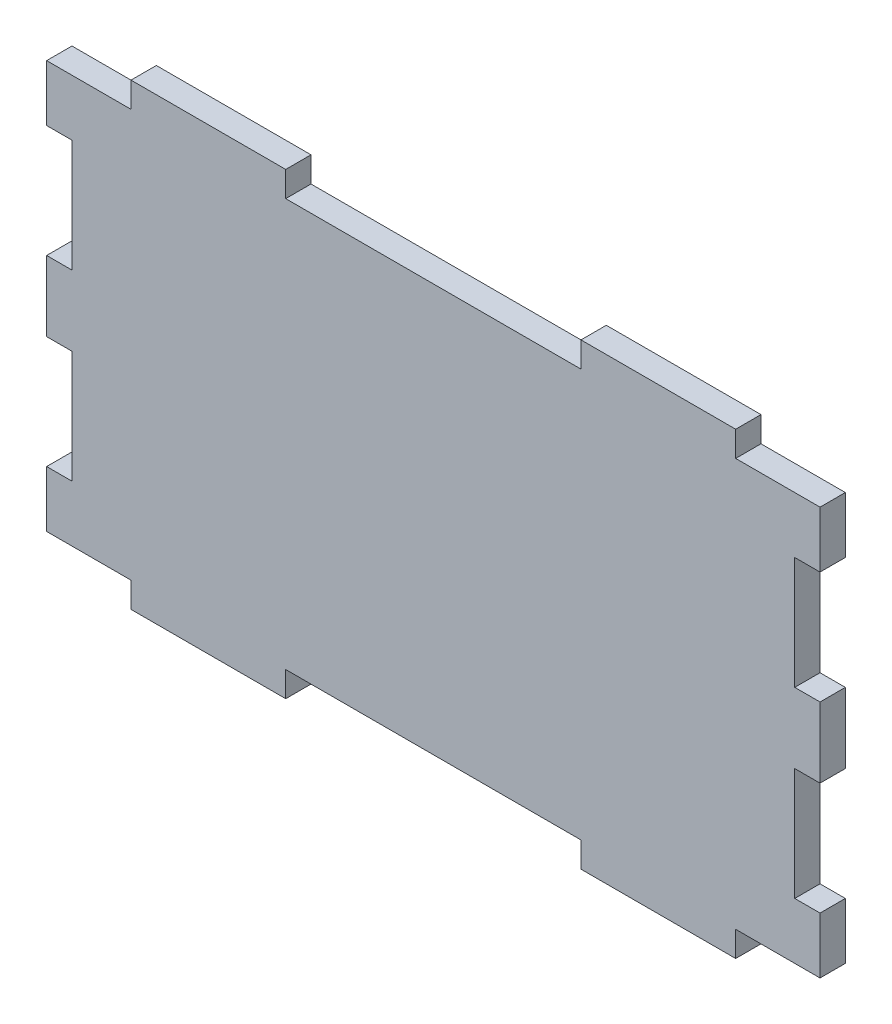
SolidWorks part; units mm, degrees
material "Бальса"
ref_plane "Спереди" through (0, 0, 0) normal (0, 0, 1) x (1, 0, 0)
ref_plane "Сверху" through (0, 0, 0) normal (0, 1, 0) x (1, 0, 0)
ref_plane "Справа" through (0, 0, 0) normal (1, 0, 0) x (0, 0, -1)
sketch "Эскиз1" plane through (0, 0, 0) normal (0, 0, 1) x (1, 0, 0)
  line L1 (0, 0) -> (110, 0)
  line L2 (0, 0) -> (0, 58)
  line L3 (0, 58) -> (110, 58)
  line L4 (110, 0) -> (110, 58)
  dimension "D1" = 110
  dimension "D2" = 58
base flange "Базовая кромка1" sketch "Эскиз1" thickness 3.6 reverse thickness direction no parameters "D1"=0.7366
sketch "Эскиз2" plane through (0, 0, -3.6) normal (0, 0, -1) x (-1, 0, 0)
  line L0 (-110, 0) -> (-110, 58) construction
  line L1 (-110, 50) -> (-106.4, 50)
  line L2 (-110, 50) -> (-110, 34)
  line L3 (-110, 34) -> (-106.4, 34)
  line L4 (-106.4, 50) -> (-106.4, 34)
  line L5 (-110, 0) -> (-110, 58) construction
  line L6 (-110, 24) -> (-106.4, 24)
  line L7 (-110, 24) -> (-110, 8)
  line L8 (-110, 8) -> (-106.4, 8)
  line L9 (-106.4, 24) -> (-106.4, 8)
  line L10 (-110, 58) -> (0, 58) construction
  line L11 (0, 0) -> (-110, 0) construction
  line L12 (-55, 58) -> (-55, 0) construction
  line L13 (-3.6, 24) -> (-3.6, 8)
  line L14 (0, 8) -> (-3.6, 8)
  line L15 (0, 24) -> (0, 8)
  line L16 (0, 24) -> (-3.6, 24)
  line L17 (-3.6, 50) -> (-3.6, 34)
  line L18 (0, 34) -> (-3.6, 34)
  line L19 (0, 50) -> (0, 34)
  line L20 (0, 50) -> (-3.6, 50)
  dimension "D1" = 8
  dimension "D2" = 16
  dimension "D3" = 8
  dimension "D4" = 16
  dimension "D5" = 3.6
extrude "Вырез-Вытянуть1" cut sketch "Эскиз2" against normal up to next normal cut yes
sketch "Эскиз3" plane through (0, 0, 0) normal (0, 0, 1) x (1, 0, 0)
  line L0 (0, 58) -> (110, 58) construction
  line L1 (12, 58) -> (34, 58)
  line L2 (12, 58) -> (12, 61.6)
  line L3 (12, 61.6) -> (34, 61.6)
  line L4 (34, 58) -> (34, 61.6)
  line L5 (110, 58) -> (0, 58) construction
  line L6 (76, 58) -> (98, 58)
  line L7 (76, 58) -> (76, 61.6)
  line L8 (76, 61.6) -> (98, 61.6)
  line L9 (98, 58) -> (98, 61.6)
  line L10 (0, 0) -> (110, 0) construction
  line L11 (12, 0) -> (34, 0)
  line L12 (12, 0) -> (12, -3.6)
  line L13 (12, -3.6) -> (34, -3.6)
  line L14 (34, 0) -> (34, -3.6)
  line L15 (0, 58) -> (0, 50) construction
  line L16 (76, 0) -> (98, 0)
  line L17 (76, 0) -> (76, -3.6)
  line L18 (76, -3.6) -> (98, -3.6)
  line L19 (98, 0) -> (98, -3.6)
  line L20 (110, 50) -> (110, 58) construction
  dimension "D1" = 12
  dimension "D2" = 12
  dimension "D3" = 22
  dimension "D4" = 22
  dimension "D5" = 3.6
  dimension "D6" = 3.6
extrude "Бобышка-Вытянуть1" add sketch "Эскиз3" against normal up to surface (3.6 mm away) up to face at (55, 29, -3.6)
sketch "Сгиб-Линии1" [suppressed] plane through (0, 0, 0) normal (0, 1, 0) x (1, 0, 0)
sketch "Граничная рамка1" [suppressed] plane through (0, 0, 0) normal (0, 1, 0) x (1, 0, 0)
sheet metal parameters "Листовой металл3" thickness 3.6 parameters "D1"=0.7366
flat pattern "Развертка3" [suppressed]
sketch "Сгиб-Линии2" plane through (0, 0, 0) normal (0, 1, 0) x (1, 0, 0)
sketch3d "Граничная рамка2" [suppressed]
  line L0 (0, 0, 0) -> (170, 0, 0) construction
  line L1 (0, 58, 0) -> (170, 58, 0) construction
  line L2 (0, 0, 0) -> (0, 58, 0) construction
  line L3 (170, 0, 0) -> (170, 58, 0) construction
sheet metal parameters "Листовой металл4" thickness 3.6 parameters "D1"=0.7366
flat pattern "Развертка3"
sketch "Сгиб-Линии2" plane through (0, 0, 0) normal (0, 1, 0) x (1, 0, 0)
sketch3d "Граничная рамка2" [suppressed]
  line L0 (0, 0, 0) -> (170, 0, 0) construction
  line L1 (0, 58, 0) -> (170, 58, 0) construction
  line L2 (0, 0, 0) -> (0, 58, 0) construction
  line L3 (170, 0, 0) -> (170, 58, 0) construction
sheet metal parameters "Листовой металл5" thickness 3.6 parameters "D1"=0.7366
flat pattern "Развертка3"
sketch "Сгиб-Линии2" plane through (0, 0, 0) normal (0, 1, 0) x (1, 0, 0)
sketch3d "Граничная рамка2" [suppressed]
  line L0 (0, 0, 0) -> (170, 0, 0) construction
  line L1 (0, 58, 0) -> (170, 58, 0) construction
  line L2 (0, 0, 0) -> (0, 58, 0) construction
  line L3 (170, 0, 0) -> (170, 58, 0) construction
